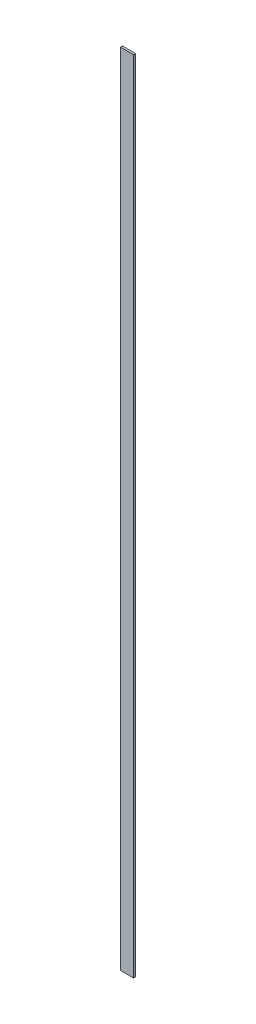
SolidWorks part; units mm, degrees
ref_plane "Front Plane" through (0, 0, 0) normal (0, 0, 1) x (1, 0, 0)
ref_plane "Top Plane" through (0, 0, 0) normal (0, 1, 0) x (1, 0, 0)
ref_plane "Right Plane" through (0, 0, 0) normal (1, 0, 0) x (0, 0, -1)
sketch "Sketch1" plane through (0, 0, -52.8112) normal (0, 0, 1) x (1, 0, 0)
  line L1 (-294.2931, 720) -> (-314.2931, 720)
  line L2 (-294.2931, 720) -> (-294.2931, -505)
  line L3 (-294.2931, -505) -> (-314.2931, -505)
  line L4 (-314.2931, 720) -> (-314.2931, -505)
  line L6 (-314.2931, -505) -> (-314.2931, 720) construction
  dimension "D1" = 1225
  dimension "D2" = 20
extrude "Boss-Extrude1" add sketch "Sketch1" along normal blind 3
